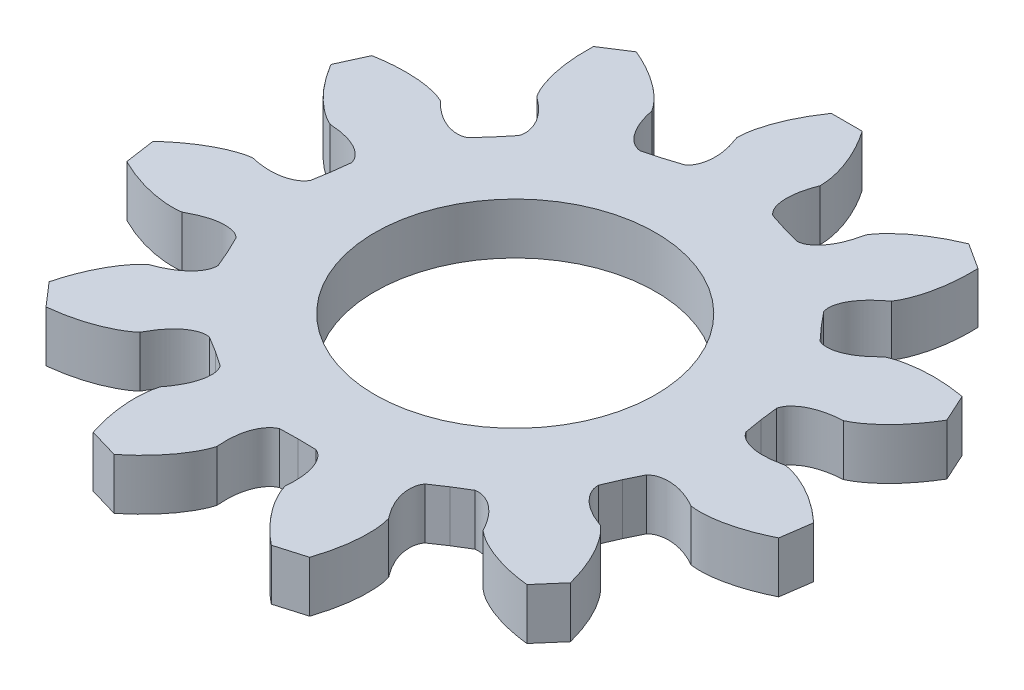
SolidWorks part; units mm, degrees
ref_plane "Plano frontal" through (0, 0, 0) normal (0, 0, 1) x (1, 0, 0)
ref_plane "Plano superior" through (0, 0, 0) normal (0, 1, 0) x (1, 0, 0)
ref_plane "Plano direito" through (0, 0, 0) normal (1, 0, 0) x (0, 0, -1)
sketch "Esboço1" plane through (0, 0, 0) normal (0, 1, 0) x (1, 0, 0)
  line L0 (-1.4172, -17.0311) -> (0, -17)
  line L1 (0, -17) -> (1.4172, -17.0311)
  line L3 (6.1555, -25.2608) -> (8.4787, -24.5787)
  line L4 (-9.1909, -14.3013) -> (-8.0155, -15.0937)
  line L5 (-10.4, -13.5613) -> (-9.1909, -14.3013)
  line L6 (-8.4787, -24.5787) -> (-6.1555, -25.2608)
  line L7 (-15.4637, -7.0621) -> (-14.9033, -8.3641)
  line L8 (-16.0808, -5.7858) -> (-15.4637, -7.0621)
  line L9 (-20.421, -16.0929) -> (-18.8353, -17.9229)
  line L10 (-16.827, 2.4193) -> (-17.0595, 1.021)
  line L11 (-16.6561, 3.8266) -> (-16.827, 2.4193)
  line L12 (-25.8797, -2.4978) -> (-25.5351, -4.8945)
  line L13 (-12.8478, 11.1326) -> (-13.7994, 10.082)
  line L14 (-11.9432, 12.2241) -> (-12.8478, 11.1326)
  line L15 (-23.1218, 11.8904) -> (-24.1277, 9.6878)
  line L16 (-4.7895, 16.3114) -> (-6.158, 15.942)
  line L17 (-3.4384, 16.7405) -> (-4.7895, 16.3114)
  line L18 (-13.0229, 22.5034) -> (-15.0599, 21.1943)
  line L19 (4.7894, 16.3114) -> (3.4384, 16.7405)
  line L20 (6.158, 15.942) -> (4.7894, 16.3114)
  line L21 (1.2107, 25.9718) -> (-1.2107, 25.9718)
  line L22 (12.8477, 11.1326) -> (11.9432, 12.2241)
  line L23 (13.7994, 10.082) -> (12.8477, 11.1326)
  line L24 (15.0599, 21.1943) -> (13.0229, 22.5034)
  line L25 (16.827, 2.4194) -> (16.6561, 3.8266)
  line L26 (17.0595, 1.021) -> (16.827, 2.4194)
  line L27 (24.1277, 9.6878) -> (23.1218, 11.8904)
  line L28 (15.4638, -7.062) -> (16.0808, -5.7858)
  line L29 (14.9033, -8.3641) -> (15.4638, -7.062)
  line L30 (25.5351, -4.8945) -> (25.8797, -2.4978)
  line L31 (9.1909, -14.3013) -> (10.4, -13.5613)
  line L32 (8.0155, -15.0937) -> (9.1909, -14.3013)
  line L33 (18.8353, -17.9229) -> (20.421, -16.0929)
  circle A1 centre (0, 0) radius 11
  spline S0 degree 3 number of poles 452 (2.6799, -20.6972) -> (6.1555, -25.2608)
  spline S1 degree 3 number of poles 332 (1.4172, -17.0311) -> (2.6799, -20.6972)
  spline S2 degree 3 number of poles 452 (8.4787, -24.5787) -> (8.9352, -18.8605)
  spline S3 degree 3 number of poles 332 (8.0155, -15.0937) -> (8.9352, -18.8605)
  spline S4 degree 3 number of poles 452 (-8.9352, -18.8605) -> (-8.4787, -24.5787)
  spline S5 degree 3 number of poles 332 (-8.0155, -15.0937) -> (-8.9352, -18.8605)
  spline S6 degree 3 number of poles 452 (-6.1555, -25.2608) -> (-2.6799, -20.6972)
  spline S7 degree 3 number of poles 332 (-1.4172, -17.0311) -> (-2.6799, -20.6972)
  spline S8 degree 3 number of poles 452 (-17.7136, -11.0357) -> (-20.421, -16.0929)
  spline S9 degree 3 number of poles 332 (-14.9033, -8.3641) -> (-17.7136, -11.0357)
  spline S10 degree 3 number of poles 452 (-18.8353, -17.9229) -> (-13.4443, -15.9627)
  spline S11 degree 3 number of poles 332 (-10.4, -13.5613) -> (-13.4443, -15.9627)
  spline S12 degree 3 number of poles 452 (-20.8679, 0.2929) -> (-25.8797, -2.4978)
  spline S13 degree 3 number of poles 332 (-17.0595, 1.021) -> (-20.8679, 0.2929)
  spline S14 degree 3 number of poles 452 (-25.5351, -4.8945) -> (-19.9401, -6.1602)
  spline S15 degree 3 number of poles 332 (-16.0808, -5.7858) -> (-19.9401, -6.1602)
  spline S16 degree 3 number of poles 452 (-17.3969, 11.5284) -> (-23.1218, 11.8904)
  spline S17 degree 3 number of poles 332 (-13.7994, 10.082) -> (-17.3969, 11.5284)
  spline S18 degree 3 number of poles 452 (-24.1277, 9.6878) -> (-20.1052, 5.5982)
  spline S19 degree 3 number of poles 332 (-16.6561, 3.8266) -> (-20.1052, 5.5982)
  spline S20 degree 3 number of poles 452 (-8.4025, 19.1038) -> (-13.0229, 22.5034)
  spline S21 degree 3 number of poles 332 (-6.158, 15.942) -> (-8.4025, 19.1038)
  spline S22 degree 3 number of poles 452 (-15.0599, 21.1943) -> (-13.8869, 15.5792)
  spline S23 degree 3 number of poles 332 (-11.9432, 12.2241) -> (-13.8869, 15.5792)
  spline S24 degree 3 number of poles 452 (3.2597, 20.6139) -> (1.2107, 25.9718)
  spline S25 degree 3 number of poles 332 (3.4384, 16.7405) -> (3.2597, 20.6139)
  spline S26 degree 3 number of poles 452 (-1.2107, 25.9718) -> (-3.2597, 20.6139)
  spline S27 degree 3 number of poles 332 (-3.4384, 16.7405) -> (-3.2597, 20.6139)
  spline S28 degree 3 number of poles 452 (13.8869, 15.5792) -> (15.0599, 21.1943)
  spline S29 degree 3 number of poles 332 (11.9432, 12.2241) -> (13.8869, 15.5792)
  spline S30 degree 3 number of poles 452 (13.0229, 22.5034) -> (8.4025, 19.1038)
  spline S31 degree 3 number of poles 332 (6.158, 15.942) -> (8.4025, 19.1038)
  spline S32 degree 3 number of poles 452 (20.1052, 5.5982) -> (24.1277, 9.6878)
  spline S33 degree 3 number of poles 332 (16.6561, 3.8266) -> (20.1052, 5.5982)
  spline S34 degree 3 number of poles 452 (23.1218, 11.8904) -> (17.3969, 11.5284)
  spline S35 degree 3 number of poles 332 (13.7994, 10.082) -> (17.3969, 11.5284)
  spline S36 degree 3 number of poles 452 (19.9401, -6.1602) -> (25.5351, -4.8945)
  spline S37 degree 3 number of poles 332 (16.0808, -5.7858) -> (19.9401, -6.1602)
  spline S38 degree 3 number of poles 452 (25.8797, -2.4978) -> (20.8679, 0.2929)
  spline S39 degree 3 number of poles 332 (17.0595, 1.021) -> (20.8679, 0.2929)
  spline S40 degree 3 number of poles 452 (13.4443, -15.9627) -> (18.8353, -17.9229)
  spline S41 degree 3 number of poles 332 (10.4, -13.5613) -> (13.4443, -15.9627)
  spline S42 degree 3 number of poles 452 (20.421, -16.0929) -> (17.7136, -11.0357)
  spline S43 degree 3 number of poles 332 (14.9033, -8.3641) -> (17.7136, -11.0357)
  point P93 (0, 0)
  dimension "D1" = 11
extrude "Ressalto-extrusão1" add sketch "Esboço1" along normal blind 4
sketch "Esboço2" plane through (0, 0, 0) normal (0, 1, 0) x (1, 0, 0)
  point P0 (0, 0)
